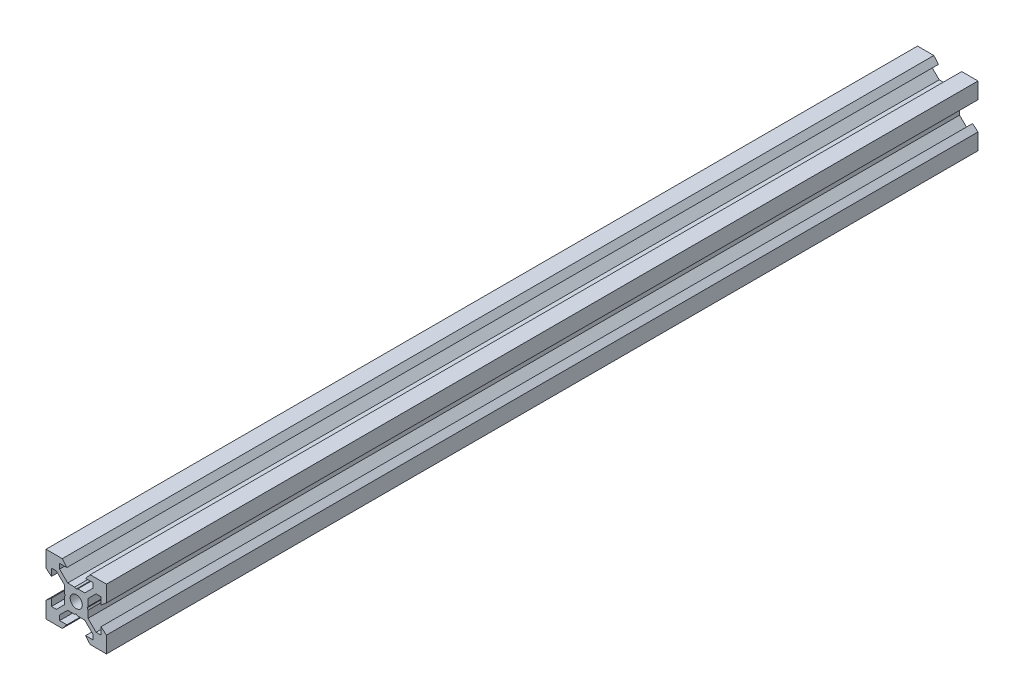
SolidWorks part; units mm, degrees
ref_plane "Front Plane" through (0, 0, 0) normal (0, 0, 1) x (1, 0, 0)
ref_plane "Top Plane" through (0, 0, 0) normal (0, 1, 0) x (1, 0, 0)
ref_plane "Right Plane" through (0, 0, 0) normal (1, 0, 0) x (0, 0, -1)
sketch "Sketch1" plane through (0, 0, 0) normal (0, 0, 1) x (1, 0, 0)
  line L0 (10, 10) -> (4.6104, 10) construction
  line L1 (10, 10) -> (10, 4.6104) construction
  line L2 (10, -10) -> (10, -4.6104) construction
  line L3 (10, -10) -> (4.6104, -10) construction
  line L4 (10, 10) -> (10, 4.6104)
  line L5 (6.5607, 5.5) -> (8.2, 5.5)
  line L6 (5.5, 8.2) -> (5.5, 6.5607)
  line L7 (10, 10) -> (4.6104, 10)
  line L8 (10, 10) -> (10, 4.6104)
  line L9 (6.5607, 5.5) -> (3.9, 2.8393)
  line L10 (5.5, 6.5607) -> (2.8393, 3.9)
  line L11 (10, 4.6104) -> (8.2, 3.1)
  line L12 (4.6104, 10) -> (3.1, 8.2)
  line L13 (8.2, 3.1) -> (8.2, 5.5)
  line L14 (3.1, 8.2) -> (5.5, 8.2)
  line L15 (-6.5607, 5.5) -> (-8.2, 5.5)
  line L16 (6.5607, -5.5) -> (8.2, -5.5)
  line L17 (3.1, -8.2) -> (5.5, -8.2)
  line L18 (8.2, -3.1) -> (8.2, -5.5)
  line L19 (4.6104, -10) -> (3.1, -8.2)
  line L20 (10, -4.6104) -> (8.2, -3.1)
  line L21 (0.5196, -3.9) -> (0, -3.6)
  line L22 (0.5196, 3.9) -> (0, 3.6)
  line L23 (3.6, 0) -> (3.9, -0.5196)
  line L24 (3.9, 0.5196) -> (3.6, 0)
  line L25 (3.9, 0.5196) -> (3.9, 2.8393)
  line L26 (2.8393, 3.9) -> (0.5196, 3.9)
  line L27 (3.9, -2.8393) -> (3.9, -0.5196)
  line L28 (2.8393, -3.9) -> (0.5196, -3.9)
  line L29 (5.5, -6.5607) -> (2.8393, -3.9)
  line L30 (6.5607, -5.5) -> (3.9, -2.8393)
  line L31 (10, -10) -> (10, -4.6104)
  line L32 (10, -10) -> (4.6104, -10)
  line L33 (5.5, -8.2) -> (5.5, -6.5607)
  line L34 (-6.5607, -5.5) -> (-8.2, -5.5)
  line L35 (10, -10) -> (10, -4.6104)
  line L36 (0, 0) -> (0, 8.2) construction
  line L37 (-10, -10) -> (-4.6104, -10) construction
  line L38 (-10, -10) -> (-10, -4.6104) construction
  line L39 (-10, 10) -> (-10, 4.6104) construction
  line L40 (-10, 10) -> (-4.6104, 10) construction
  line L41 (-10, -10) -> (-10, -4.6104)
  line L43 (-5.5, -8.2) -> (-5.5, -6.5607)
  line L44 (-10, -10) -> (-4.6104, -10)
  line L45 (-10, -10) -> (-10, -4.6104)
  line L46 (-6.5607, -5.5) -> (-3.9, -2.8393)
  line L47 (-5.5, -6.5607) -> (-2.8393, -3.9)
  line L48 (-2.8393, -3.9) -> (-0.5196, -3.9)
  line L49 (-3.9, -2.8393) -> (-3.9, -0.5196)
  line L50 (-2.8393, 3.9) -> (-0.5196, 3.9)
  line L51 (-3.9, 0.5196) -> (-3.9, 2.8393)
  line L52 (-3.9, 0.5196) -> (-3.6, 0)
  line L53 (-3.6, 0) -> (-3.9, -0.5196)
  line L54 (-0.5196, 3.9) -> (0, 3.6)
  line L55 (-0.5196, -3.9) -> (0, -3.6)
  line L56 (-10, -4.6104) -> (-8.2, -3.1)
  line L57 (-4.6104, -10) -> (-3.1, -8.2)
  line L58 (-8.2, -3.1) -> (-8.2, -5.5)
  line L59 (-3.1, -8.2) -> (-5.5, -8.2)
  line L60 (-10, -10) -> (10, -10) construction
  line L61 (-10, -10) -> (-10, 10) construction
  line L62 (-3.1, 8.2) -> (-5.5, 8.2)
  line L63 (-8.2, 3.1) -> (-8.2, 5.5)
  line L64 (-4.6104, 10) -> (-3.1, 8.2)
  line L65 (-10, 4.6104) -> (-8.2, 3.1)
  line L66 (-5.5, 6.5607) -> (-2.8393, 3.9)
  line L67 (-6.5607, 5.5) -> (-3.9, 2.8393)
  line L68 (-10, 10) -> (-10, 4.6104)
  line L69 (-10, 10) -> (-4.6104, 10)
  line L70 (-5.5, 8.2) -> (-5.5, 6.5607)
  line L71 (-10, 10) -> (10, 10) construction
  line L72 (-10, 10) -> (-10, 4.6104)
  line L73 (10, -10) -> (10, 10) construction
  line L74 (-10, -10) -> (10, 10) construction
  line L75 (-10, 10) -> (10, -10) construction
  circle A0 centre (0, 0) radius 2
  dimension "D7" = 4
  dimension "D1" = 20
  dimension "D2" = 5.3896
  dimension "D3" = 4.5
  dimension "D4" = 50
  dimension "D5" = 1.8
  dimension "D6" = 1.5104
  dimension "D8" = 5.5
  dimension "D9" = 120
  dimension "D10" = 0.3
  dimension "D11" = 2.3197
  dimension "D12" = 7.8
  dimension "D13" = 7.8
  dimension "D14" = 1.5
  dimension "D15" = 2.6607
extrude "Boss-Extrude1" add sketch "Sketch1" along normal mid plane 288.33 contours L70 L62 L64 L69 L68 L65 L63 L15 L67 L51 L52 L53 L49 L46 L34 L58 L56 L41 L44 L57 L59 L43 L47 L48 L55 L21 L28 L29 L33 L17 L19 L32 L31 L20 L18 L16 L30 L27 L23 L24 L25 L9 L5 L13 L11 L4 L7 L12 L14 L6 L10 region at (9.7172, 7.3052, 0)
